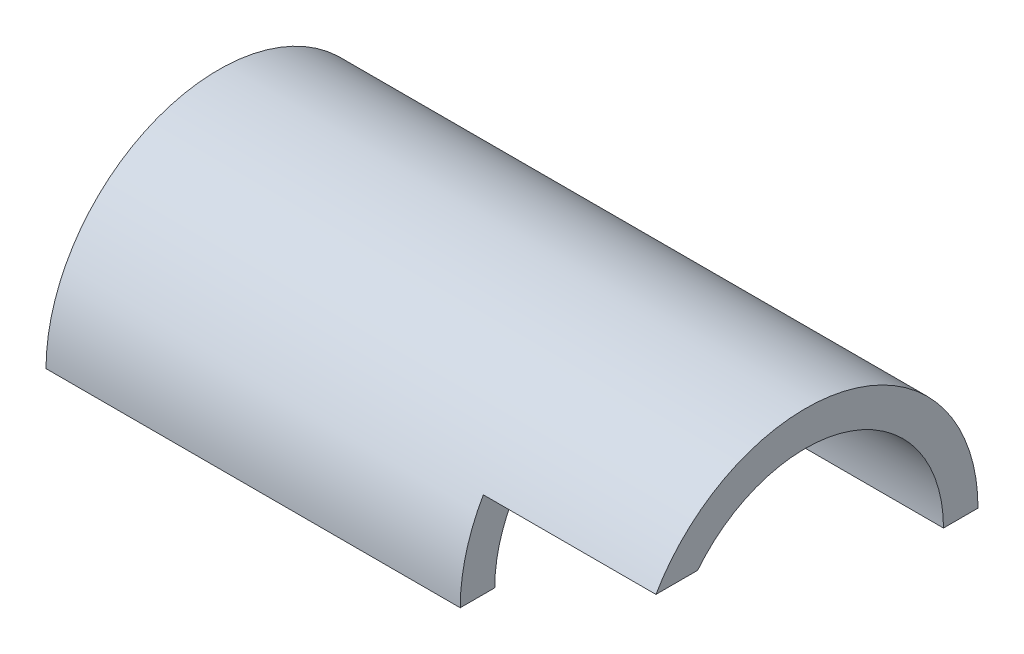
SolidWorks part; units mm, degrees
ref_plane "Front Plane" through (0, 0, 0) normal (0, 0, 1) x (1, 0, 0)
ref_plane "Top Plane" through (0, 0, 0) normal (0, 1, 0) x (1, 0, 0)
ref_plane "Right Plane" through (0, 0, 0) normal (1, 0, 0) x (0, 0, -1)
sketch "Sketch1" plane through (0, 0, 0) normal (1, 0, 0) x (0, 0, -1)
  line L0 (-31.75, 0) -> (-25.4, 0)
  line L1 (25.4, 0) -> (31.75, 0)
  arc A0 (-31.75, 0) -> (31.75, 0) centre (0, 0) cw
  arc A1 (-25.4, 0) -> (25.4, 0) centre (0, 0) cw
  dimension "D1" = 25.4
  dimension "D2" = 31.75
  dimension "D3" = 6.35
  dimension "D4" = 6.35
extrude "Boss-Extrude1" add sketch "Sketch1" against normal blind 107.95
sketch "Sketch2" plane through (0, 0, 0) normal (0, 0, 1) x (1, 0, 0)
  line L0 (-107.95, 0) -> (0, 0) construction
  line L1 (-31.75, 0) -> (0, 0)
  line L2 (-31.75, 0) -> (-31.75, 15.875)
  line L3 (-31.75, 15.875) -> (0, 15.875)
  line L4 (0, 0) -> (0, 15.875)
  line L5 (-107.95, 31.75) -> (-107.95, 0) construction
  dimension "D1" = 76.2
  dimension "D2" = 15.875
  dimension "D3" = 31.75
extrude "Cut-Extrude1" cut sketch "Sketch2" along normal blind 127
